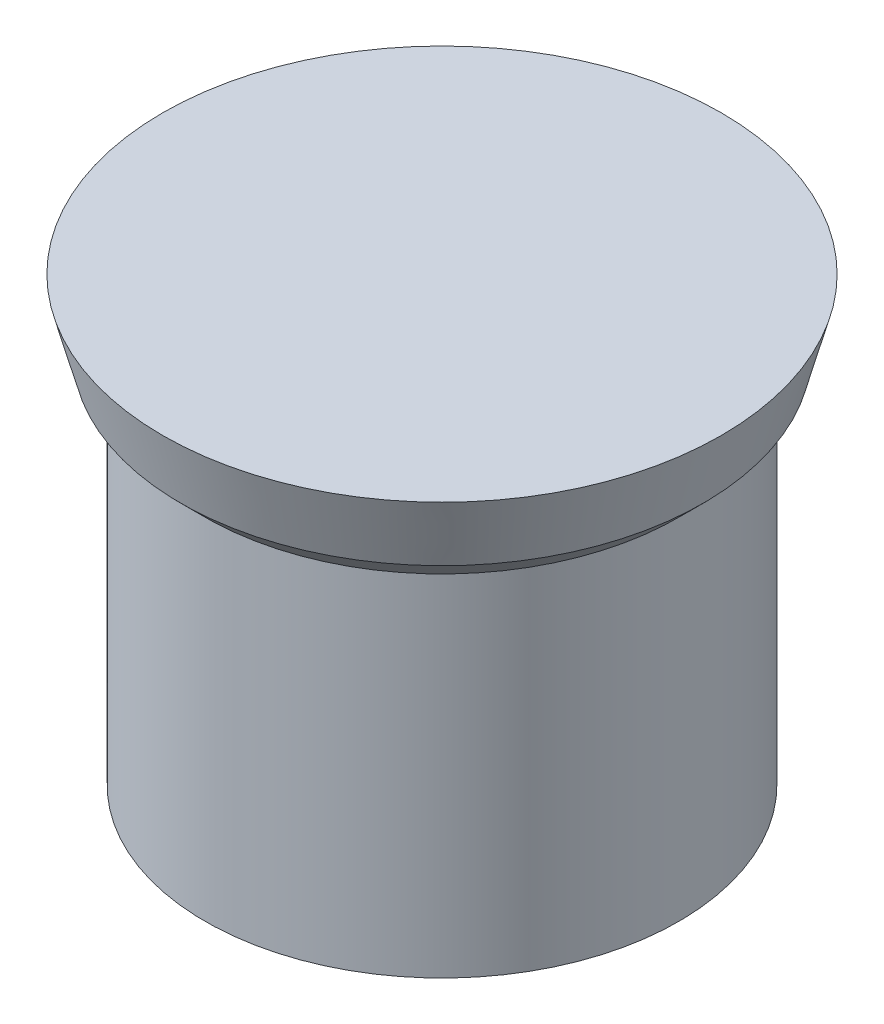
SolidWorks part; units mm, degrees
ref_plane "Front Plane" through (0, 0, 0) normal (0, 0, 1) x (1, 0, 0)
ref_plane "Top Plane" through (0, 0, 0) normal (0, 1, 0) x (1, 0, 0)
ref_plane "Right Plane" through (0, 0, 0) normal (1, 0, 0) x (0, 0, -1)
sketch "Sketch1" plane through (0, 0, 0) normal (0, 0, 1) x (1, 0, 0)
  line L0 (0, 0) -> (0, 22.6586) construction
  line L1 (0, 0) -> (0, 16.3)
  line L2 (0, 16.3) -> (10.3, 16.3)
  line L3 (10.3, 16.3) -> (9.6301, 13.8)
  line L4 (10.3, 16.3) -> (10.3, 8.1674) construction
  line L5 (9.6301, 13.8) -> (8.7312, 12.9011)
  line L6 (8.7312, 0) -> (8.7312, 12.9011)
  line L7 (9.525, 16.3) -> (9.525, 2) construction
  line L8 (0, 0) -> (8.7312, 0)
  line L9 (9.525, 2) -> (0, 2) construction
  dimension "D1" = 20.6
  dimension "D2" = 15
  dimension "D3" = 2.5
  dimension "D4" = 2
  dimension "D5" = 45
  dimension "D6" = 17.4625
  dimension "D7" = 14.3
  dimension "D8" = 19.05
revolve "Revolve1" add sketch "Sketch1" angle 360 about L0
